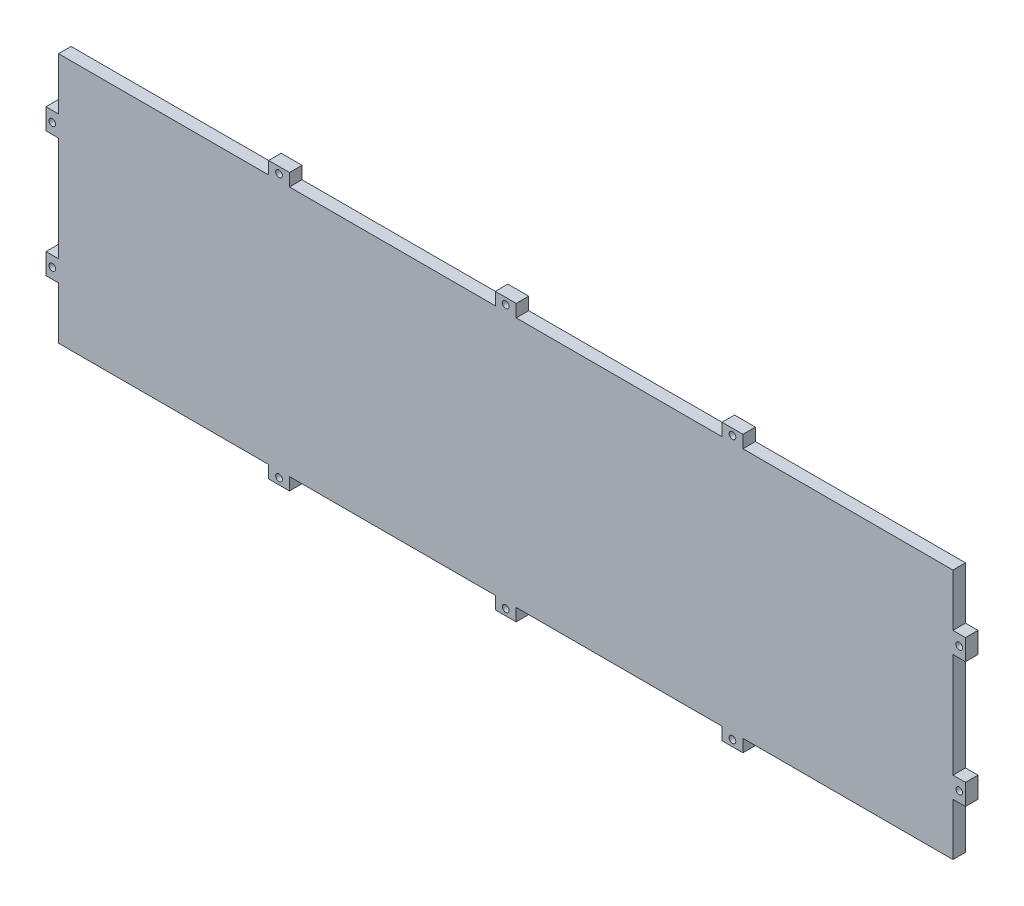
SolidWorks part; units mm, degrees
ref_plane "Front Plane" through (0, 0, 0) normal (0, 0, 1) x (1, 0, 0)
ref_plane "Top Plane" through (0, 0, 0) normal (0, 1, 0) x (1, 0, 0)
ref_plane "Right Plane" through (0, 0, 0) normal (1, 0, 0) x (0, 0, -1)
sketch "Sketch1" plane through (0, 0, 0) normal (0, 0, 1) x (1, 0, 0)
  line L0 (109.9, 127) -> (113.1, 127) construction
  line L1 (6, 250) -> (106.5, 250)
  line L2 (6, 250) -> (6, 225)
  line L3 (6, 130) -> (106.5, 130)
  line L4 (434, 250) -> (434, 225)
  line L5 (109.9, 130) -> (109.9, 124) construction
  line L6 (113.1, 124) -> (113.1, 130) construction
  line L7 (218.4, 127) -> (221.6, 127) construction
  line L8 (218.4, 130) -> (218.4, 124) construction
  line L9 (221.6, 124) -> (221.6, 130) construction
  line L10 (326.9, 127) -> (330.1, 127) construction
  line L11 (326.9, 130) -> (326.9, 124) construction
  line L12 (330.1, 124) -> (330.1, 130) construction
  line L13 (116.5, 130) -> (215, 130)
  line L14 (106.5, 124) -> (116.5, 124)
  line L15 (106.5, 124) -> (106.5, 130)
  line L16 (225, 130) -> (323.5, 130)
  line L17 (116.5, 124) -> (116.5, 130)
  line L18 (106.5, 124) -> (116.5, 130) construction
  line L19 (106.5, 130) -> (116.5, 124) construction
  line L20 (215, 124) -> (225, 124)
  line L21 (215, 124) -> (215, 130)
  line L22 (333.5, 130) -> (434, 130)
  line L23 (225, 124) -> (225, 130)
  line L24 (215, 124) -> (225, 130) construction
  line L25 (215, 130) -> (225, 124) construction
  line L26 (323.5, 124) -> (333.5, 124)
  line L27 (323.5, 124) -> (323.5, 130)
  line L28 (6, 190) -> (434, 190) construction
  line L29 (333.5, 124) -> (333.5, 130)
  line L30 (323.5, 124) -> (333.5, 130) construction
  line L31 (323.5, 130) -> (333.5, 124) construction
  line L32 (323.5, 256) -> (323.5, 250)
  line L33 (323.5, 256) -> (333.5, 256)
  line L34 (333.5, 256) -> (333.5, 250)
  line L35 (215, 256) -> (215, 250)
  line L36 (215, 256) -> (225, 256)
  line L37 (225, 256) -> (225, 250)
  line L38 (106.5, 256) -> (106.5, 250)
  line L39 (116.5, 256) -> (116.5, 250)
  line L40 (106.5, 256) -> (116.5, 256)
  line L41 (333.5, 250) -> (434, 250)
  line L42 (225, 250) -> (323.5, 250)
  line L43 (116.5, 250) -> (215, 250)
  line L44 (0, 250) -> (6, 190) construction
  line L45 (6, 215) -> (6, 165)
  line L46 (0, 215) -> (6, 215)
  line L47 (0, 215) -> (0, 225)
  line L48 (0, 225) -> (6, 225)
  line L49 (0, 250) -> (0, 225) construction
  line L50 (0, 215) -> (6, 225) construction
  line L51 (0, 225) -> (6, 215) construction
  line L52 (0, 155) -> (6, 155)
  line L53 (0, 165) -> (0, 155)
  line L54 (0, 165) -> (6, 165)
  line L55 (220, 190) -> (220, 221.6948) construction
  line L56 (440, 165) -> (434, 165)
  line L57 (440, 165) -> (440, 155)
  line L58 (440, 155) -> (434, 155)
  line L59 (440, 215) -> (434, 215)
  line L60 (440, 215) -> (440, 225)
  line L61 (440, 225) -> (434, 225)
  line L62 (6, 155) -> (6, 130)
  line L63 (434, 155) -> (434, 130)
  line L64 (434, 215) -> (434, 165)
  circle A0 centre (111.5, 127) radius 1.6
  circle A1 centre (220, 127) radius 1.6
  circle A2 centre (328.5, 127) radius 1.6
  circle A3 centre (328.5, 253) radius 1.6
  circle A4 centre (220, 253) radius 1.6
  circle A5 centre (111.5, 253) radius 1.6
  circle A6 centre (3, 220) radius 1.6
  circle A7 centre (3, 160) radius 1.6
  circle A8 centre (437, 220) radius 1.6
  circle A9 centre (437, 160) radius 1.6
  point P24 (111.5, 127)
  point P29 (220, 127)
  point P34 (328.5, 127)
  point P47 (106.5, 127)
  point P66 (106.5, 253)
  point P68 (3, 220)
  dimension "D3" = 3.2
  dimension "D1" = 10
  dimension "D2" = 10
extrude "Boss-Extrude1" add sketch "Sketch1" against normal blind 6
